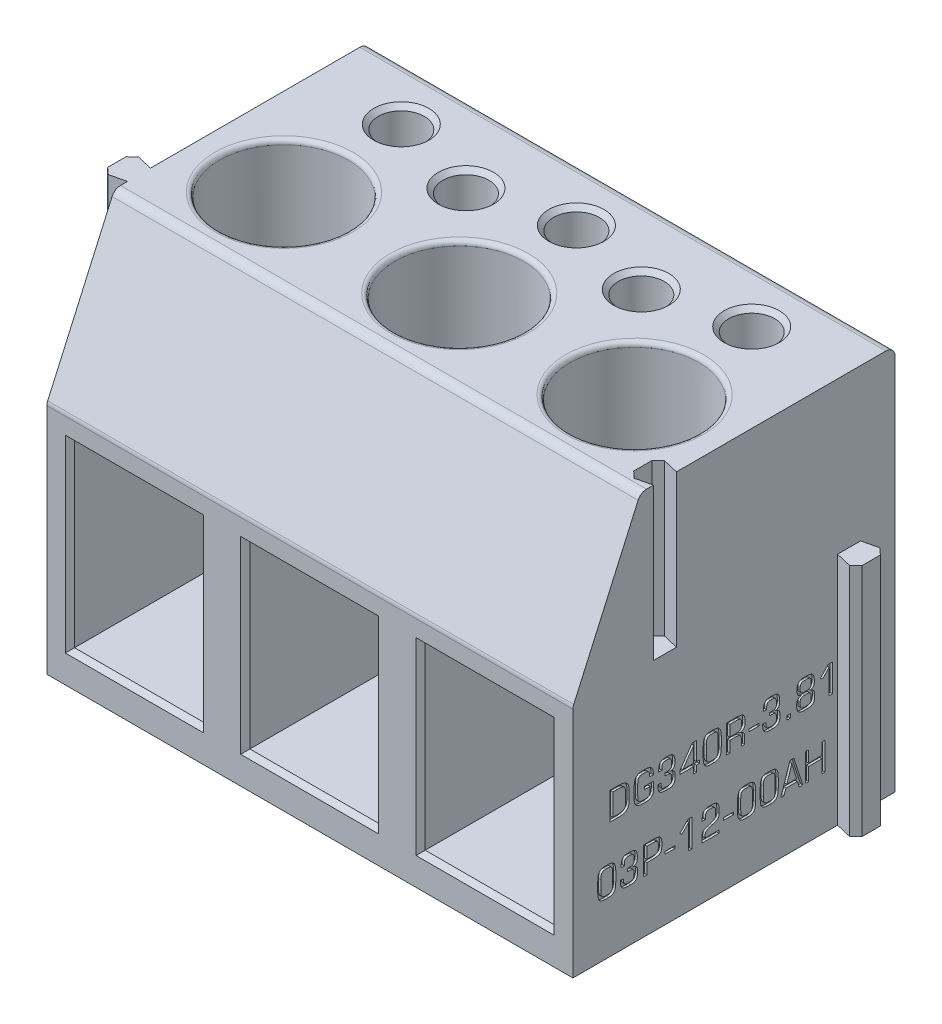
SolidWorks part; units mm, degrees
ref_plane "Спереди" through (0, 0, 0) normal (0, 0, 1) x (1, 0, 0)
ref_plane "Сверху" through (0, 0, 0) normal (0, 1, 0) x (1, 0, 0)
ref_plane "Справа" through (0, 0, 0) normal (1, 0, 0) x (0, 0, -1)
sketch "Эскиз1" plane through (0, 0, 0) normal (1, 0, 0) x (0, 0, -1)
  line L0 (-2.0307, 4.2) -> (-2.0307, -4.2) construction
  line L1 (-2.0307, 4.2) -> (3.5, 4.2)
  line L2 (-3.5, 0.9) -> (-3.5, -4.2)
  line L3 (-3.5, -4.2) -> (3.5, -4.2)
  line L4 (3.5, 4.2) -> (3.5, -4.2)
  line L5 (-2.5424, 3.0509) -> (3.5, -4.2) construction
  line L6 (-3.5, -4.2) -> (3.5, 4.2) construction
  line L7 (-2.0307, 4.2) -> (-3.5, 0.9)
  point P0 (0, 0)
  dimension "D1" = 7
  dimension "D2" = 8.4
  dimension "D5" = 5.1
  dimension "D3" = 66
extrude "Бобышка-Вытянуть1" add sketch "Эскиз1" along normal blind 11.43
sketch "Эскиз2" plane through (0, 4.2, 0) normal (0, 1, 0) x (1, 0, 0)
  line L0 (1.905, 3.5) -> (1.905, -2.25) construction
  line L3 (0, 3.5) -> (11.43, 3.5) construction
  line L4 (0, 1.8) -> (11.43, 1.8) construction
  line L5 (3.805, 2.3) -> (3.805, 1.3) construction
  line L6 (0, 3.5) -> (0, -2.0307) construction
  line L7 (3.805, 3.5) -> (3.805, -2.0307) construction
  circle A1 centre (3.805, 1.8) radius 0.5
  circle A2 centre (5.705, 2.3) radius 0.5
  dimension "D1" = 1.9
  dimension "D4" = 1.9
  dimension "D2" = 1.7
  dimension "D5" = 1.905
extrude "Вырез-Вытянуть1" cut sketch "Эскиз2" against normal blind 3.82
chamfer "Фаска1" distance 0.1 angle 45 2 edges at (3.805, 4.2, -1.3) (5.705, 4.2, -2.8)
sketch "Эскиз3" plane through (0, 0, 3.5) normal (0, 0, 1) x (1, 0, 0)
  line L2 (11.43, -4.2) -> (0, -4.2) construction
  line L9 (5.715, 0.9) -> (5.715, -4.2) construction
  line L10 (11.43, 0.9) -> (0, 0.9) construction
  line L11 (3.3, -3.5) -> (0.5, 0.4) construction
  line L12 (3.3, 0.4) -> (0.5, -3.5) construction
  line L13 (1.9, 1.3925) -> (1.9, -4.2) construction
  line L14 (0, 1.3925) -> (0, -4.2) construction
  line L15 (0.5, 0.4) -> (0.5, -3.5)
  line L16 (3.3, -3.5) -> (0.5, -3.5)
  line L17 (3.3, 0.4) -> (3.3, -3.5)
  line L18 (3.3, 0.4) -> (0.5, 0.4)
  point P25 (1.9, -1.55)
  dimension "D2" = 2.8
  dimension "D3" = 3.9
  dimension "D1" = 0.7
extrude "Вырез-Вытянуть2" cut sketch "Эскиз3" against normal blind 6.3
chamfer "Фаска2" distance 0.1 angle 45 4 edges at (1.9, -3.5, 3.5) (0.5, -1.55, 3.5) (1.9, 0.4, 3.5) (3.3, -1.55, 3.5)
sketch "Эскиз4" plane through (0, 4.2, 0) normal (0, 1, 0) x (1, 0, 0)
  line L0 (1.9, 3.5) -> (1.9, -2.0307) construction
  line L1 (11.43, -2.0307) -> (0, -2.0307) construction
  line L2 (0, 3.5) -> (11.43, 3.5) construction
  line L3 (11.43, 3.5) -> (0, 3.5) construction
  line L4 (0, 3.5) -> (0, -2.0307) construction
  circle A0 centre (1.9, -0.25) radius 1.4
  dimension "D1" = 2.8
  dimension "D2" = 3.75
  dimension "D3" = 1.9
extrude "Вырез-Вытянуть3" cut sketch "Эскиз4" against normal offset from surface (3.1 mm away) 0.7 up to face at (1.9, 0.4, 0.3)
sketch "Эскиз5" plane through (0, 1.1, 0) normal (0, 1, 0) x (1, 0, 0)
  circle A0 centre (1.9, -0.25) radius 1
  dimension "D1" = 2
extrude "Вырез-Вытянуть4" cut sketch "Эскиз5" against normal blind 1
fillet "Скругление1" radius 0.1 1 edges at (1.9, 4.2, 1.65)
sketch "Эскиз7" plane through (0, -4.2, 0) normal (0, -1, 0) x (1, 0, 0)
  line L0 (11.43, -2.75) -> (11.77, -2.83)
  line L1 (11.43, -3.5) -> (0, -3.5) construction
  line L2 (11.43, -2.5) -> (11.43, -2.75)
  line L3 (11.43, 3.5) -> (11.43, -3.5) construction
  line L4 (11.77, -2.5) -> (11.77, -2.83) construction
  line L5 (11.43, -2.5) -> (11.91, -2.5) construction
  line L6 (11.91, -2.3) -> (11.91, -2.7)
  line L7 (11.91, -2.7) -> (11.77, -2.83)
  line L8 (11.91, -2.3) -> (11.77, -2.17)
  line L9 (11.43, -2.25) -> (11.77, -2.17)
  line L10 (11.43, -2.5) -> (11.43, -2.25)
  dimension "D1" = 1
  dimension "D2" = 0.48
  dimension "D3" = 0.25
  dimension "D5" = 0.33
  dimension "D4" = 0.14
  dimension "D6" = 0.2
extrude "Бобышка-Вытянуть2" add sketch "Эскиз7" against normal blind 5.1 separate body
sketch "Эскиз8" plane through (0, -4.2, 0) normal (0, -1, 0) x (1, 0, 0)
  line L0 (0, -2.75) -> (0.34, -2.83)
  line L1 (0, -2.5) -> (0, -2.75)
  line L2 (0.34, -2.5) -> (0.34, -2.83) construction
  line L3 (0, -2.5) -> (0.48, -2.5) construction
  line L4 (0.48, -2.3) -> (0.48, -2.7)
  line L5 (0.48, -2.7) -> (0.34, -2.83)
  line L6 (0.48, -2.3) -> (0.34, -2.17)
  line L7 (0, -2.25) -> (0.34, -2.17)
  line L8 (0, -2.5) -> (0, -2.25)
  line L9 (0, -3.5) -> (0, 0) construction
  line L10 (11.43, -2.5) -> (0, -2.5) construction
  line L11 (11.43, -2.25) -> (11.43, -2.75) construction
  dimension "D1" = 0.48
  dimension "D2" = 0.25
  dimension "D3" = 0.33
  dimension "D4" = 0.2
  dimension "D5" = 0.14
extrude "Вырез-Вытянуть6" cut sketch "Эскиз8" against normal blind 5.1
sketch "Эскиз10" plane through (0, 4.2, 0) normal (0, 1, 0) x (1, 0, 0)
  line L0 (0, -1.25) -> (-0.34, -1.17)
  line L1 (0, -1.5) -> (0, -1.25)
  line L2 (-0.34, -1.5) -> (-0.34, -1.17) construction
  line L3 (0, -1.5) -> (-0.48, -1.5) construction
  line L4 (-0.48, -1.7) -> (-0.48, -1.3)
  line L5 (-0.48, -1.3) -> (-0.34, -1.17)
  line L6 (-0.48, -1.7) -> (-0.34, -1.83)
  line L7 (0, -1.75) -> (-0.34, -1.83)
  line L8 (0, -1.5) -> (0, -1.75)
  line L9 (0, -2.0307) -> (0, -1.0269) construction
  line L10 (0, 3.5) -> (0, -2.0307) construction
  line L11 (0, 3.5) -> (7.62, 3.5) construction
  line L12 (11.43, 3.5) -> (0, 3.5) construction
  dimension "D1" = 0.48
  dimension "D2" = 0.25
  dimension "D3" = 0.33
  dimension "D4" = 0.2
  dimension "D5" = 0.14
  dimension "D6" = 5
extrude "Бобышка-Вытянуть3" add sketch "Эскиз10" against normal up to surface (3.3 mm away) up to face at (0.2733, 0.9, -2.5)
sketch "Эскиз11" plane through (0, 4.2, 0) normal (0, 1, 0) x (1, 0, 0)
  line L0 (11.43, -1.25) -> (11.09, -1.17)
  line L1 (11.43, -1.5) -> (11.43, -1.25)
  line L2 (11.09, -1.5) -> (11.09, -1.17) construction
  line L3 (11.43, -1.5) -> (10.95, -1.5) construction
  line L4 (10.95, -1.7) -> (10.95, -1.3)
  line L5 (10.95, -1.3) -> (11.09, -1.17)
  line L6 (10.95, -1.7) -> (11.09, -1.83)
  line L7 (11.43, -1.75) -> (11.09, -1.83)
  line L8 (11.43, -1.5) -> (11.43, -1.75)
  line L9 (11.43, -2.0307) -> (11.43, -1.0752) construction
  line L10 (11.43, 3.5) -> (11.43, -2.0307) construction
  line L11 (-0.48, -1.5) -> (11.43, -1.5) construction
  line L12 (-0.48, -1.3) -> (-0.48, -1.7) construction
  dimension "D1" = 0.25
  dimension "D2" = 0.33
  dimension "D3" = 0.2
  dimension "D4" = 0.14
  dimension "D5" = 0.48
extrude "Вырез-Вытянуть7" cut sketch "Эскиз11" against normal up to surface (3.3 mm away) up to face at (-0.2733, 0.9, 1.5)
fillet "Скругление5" radius 0.2 1 edges at (5.715, 4.2, 2.0307)
fillet "Скругление6" radius 0.2 1 edges at (5.715, 0.9, 3.5)
fillet "Скругление7" radius 0.2 1 edges at (5.715, 4.2, -3.5)
sketch "Эскиз12" plane through (0, 0, 0) normal (-1, 0, 0) x (0, 0, 1)
  line L0 (3.5, -1.6713) -> (-2.25, -1.65) construction
  line L1 (3.5, 0.8575) -> (3.5, -4.2) construction
  line L2 (-2.25, 0.9) -> (-2.25, -4.2) construction
  text T0 "DEGSON" font "Square721 BT" height in points 4
extrude "Вырез-Вытянуть8" cut sketch "Эскиз12" against normal blind 0.05
sketch "Эскиз13" plane through (11.43, 0, 0) normal (1, 0, 0) x (0, 0, -1)
  line L0 (-3.5, -1.6713) -> (3.5, -1.6713) construction
  line L1 (-3.5, 0.8575) -> (-3.5, -4.2) construction
  line L2 (3.5, -4.2) -> (3.5, 4) construction
  text T0 "   DG340R-3.81\r\n  03P-12-00AH" font "Square721 Cn BT" height 0.6
extrude "Mark" cut sketch "Эскиз13" against normal blind 0.05
sketch "Эскиз14" plane through (0, 4.2, 0) normal (0, 1, 0) x (1, 0, 0)
  line L0 (0, 3.5) -> (11.43, 3.5) construction
  line L1 (0, 3.3) -> (0, -1.25) construction
  circle A0 centre (1.9, 2.3) radius 0.5
  dimension "D1" = 1
  dimension "D2" = 1.2
  dimension "D3" = 1.9
extrude "Вырез-Вытянуть10" cut sketch "Эскиз14" against normal up to surface (3.8 mm away) up to face at (0.9, 0.4, 0.25)
chamfer "Фаска3" distance 0.1 angle 45 1 edges at (1.9, 4.2, -1.8)
pattern_linear "Линейный массив12" count 2 spacing 3.81 along (1, 0, 0) of "Вырез-Вытянуть1", "Фаска1"
sketch "Эскиз15" plane through (0, 0, -3.5) normal (0, 0, -1) x (-1, 0, 0)
  line L4 (0, -4.2) -> (0, 4)
  line L5 (0, 4) -> (-11.43, 4)
  line L6 (-11.43, 4) -> (-11.43, -4.2)
  line L7 (-11.43, -4.2) -> (0, -4.2)
  line L8 (0, -4.2) -> (0, 4) construction
  line L9 (0, 4) -> (-11.43, 4) construction
  line L10 (-11.43, 4) -> (-11.43, -4.2) construction
  line L11 (-11.43, -4.2) -> (0, -4.2) construction
  circle A0 centre (-1.9, -2.05) radius 0.425
  dimension "D4" = 0.85
  dimension "D2" = 1.9
  dimension "D3" = 2.15
  dimension "D1" = 0
extrude "Вырез-Вытянуть11" cut sketch "Эскиз15" against normal up to surface (0.7 mm away) up to face at (1.9, -1.16, -2.8)
fillet "Скругление8" radius 0.1 1 edges at (1.9, -1.625, -3.5)
pattern_linear "Линейный массив15" count 3 spacing 3.81 along (1, 0, 0) of "Вырез-Вытянуть2", "Вырез-Вытянуть11", "Вырез-Вытянуть3", "Вырез-Вытянуть4", "Фаска2", "Скругление1", "Скругление8"
